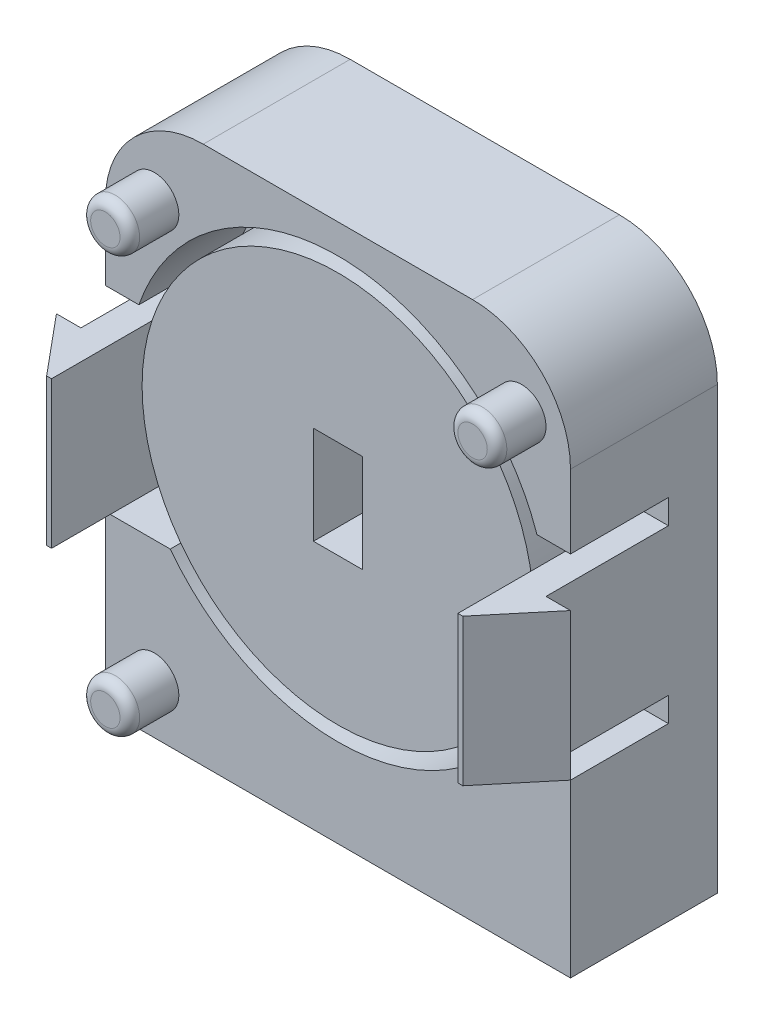
SolidWorks part; units mm, degrees
ref_plane "Front Plane" through (0, 0, 0) normal (0, 0, 1) x (1, 0, 0)
ref_plane "Top Plane" through (0, 0, 0) normal (0, 1, 0) x (1, 0, 0)
ref_plane "Right Plane" through (0, 0, 0) normal (1, 0, 0) x (0, 0, -1)
sketch "Sketch1" plane through (0, 0, 0) normal (0, 0, 1) x (1, 0, 0)
  line L1 (-4.75, -5.5) -> (4.75, -5.5)
  line L2 (-4.75, -5.5) -> (-4.75, 5.5)
  line L3 (-4.75, 5.5) -> (4.75, 5.5)
  line L4 (4.75, -5.5) -> (4.75, 5.5)
  line L5 (-4.75, -5.5) -> (4.75, 5.5) construction
  line L6 (-4.75, 5.5) -> (4.75, -5.5) construction
  point P0 (0, 0)
  dimension "D1" = 11
  dimension "D2" = 9.5
extrude "Boss-Extrude1" add sketch "Sketch1" along normal blind 3
sketch "Sketch2" plane through (0, 0, 3) normal (0, 0, 1) x (1, 0, 0)
  line L0 (0, 5.5) -> (0, -5.5) construction
  line L1 (4.75, 5.5) -> (-4.75, 5.5) construction
  line L2 (-4.75, -5.5) -> (4.75, -5.5) construction
  circle A0 centre (0, 0.6) radius 4.3
  dimension "D1" = 0.6
  dimension "D2" = 8.6
extrude "Cut-Extrude1" cut sketch "Sketch2" against normal offset from surface (2 mm away) 1 up to face at (0, 0, 0)
fillet "Fillet1" radius 2 2 edges at (-4.75, 5.5, 1.5) (4.75, 5.5, 1.5)
sketch "Sketch3" plane through (0, 0, 3) normal (0, 0, 1) x (1, 0, 0)
  line L0 (4.75, -5.5) -> (4.75, 3.5) construction
  line L1 (-4.75, 2) -> (4.75, 2)
  line L2 (-4.75, 2) -> (-4.75, -2)
  line L3 (-4.75, -2) -> (4.75, -2)
  line L4 (4.75, 2) -> (4.75, -2)
  line L5 (-4.75, 3.5) -> (-4.75, -5.5) construction
  line L6 (2.75, 5.5) -> (-2.75, 5.5) construction
  line L7 (-4.75, -5.5) -> (4.75, -5.5) construction
  dimension "D1" = 3.5
  dimension "D2" = 3.5
extrude "Cut-Extrude2" cut sketch "Sketch3" against normal up to surface (2 mm away) up to face at (-4.3, 0.6, 1)
sketch "Sketch4" plane through (0, 0, 1) normal (0, 0, 1) x (1, 0, 0)
  line L0 (-4.75, 2) -> (-4.75, -2) construction
  line L1 (-4.75, 1.5) -> (-4.15, 1.5)
  line L2 (-4.75, 1.5) -> (-4.75, -1.5)
  line L3 (-4.75, -1.5) -> (-4.15, -1.5)
  line L4 (-4.15, 1.5) -> (-4.15, -1.5)
  line L7 (-4.75, 2) -> (-4.75, 1.5) construction
  line L8 (-4.75, -1.5) -> (-4.75, -2) construction
  line L9 (4.75, -2) -> (4.75, 2) construction
  line L10 (4.75, 1.5) -> (4.15, 1.5)
  line L11 (4.75, 1.5) -> (4.75, -1.5)
  line L12 (4.75, -1.5) -> (4.15, -1.5)
  line L13 (4.15, 1.5) -> (4.15, -1.5)
  dimension "D1" = 0.6
  dimension "D2" = 3
extrude "Boss-Extrude2" add sketch "Sketch4" along normal offset from surface (3.7 mm away) 1.7 up to face at (0, 3.7161, 3) offset beyond the face yes
sketch "Sketch5" plane through (0, -1.5, 0) normal (0, -1, 0) x (1, 0, 0)
  line L2 (4.75, 4.7) -> (5.25, 4.7)
  line L3 (4.75, 4.7) -> (4.75, 3.5)
  line L4 (4.75, 3.5) -> (5.25, 3.5)
  line L5 (5.25, 4.7) -> (5.25, 3.5)
  line L6 (-4.75, 4.7) -> (-5.25, 4.7)
  line L7 (-4.75, 4.7) -> (-4.75, 3.5)
  line L8 (-4.75, 3.5) -> (-5.25, 3.5)
  line L9 (-5.25, 4.7) -> (-5.25, 3.5)
  dimension "D1" = 0.5
  dimension "D2" = 1.2
extrude "Boss-Extrude3" add sketch "Sketch5" against normal up to surface (3 mm away) up to face at (-4.45, 1.5, 2.85)
sketch "Sketch6" plane through (0, -1.5, 0) normal (0, -1, 0) x (1, 0, 0)
  line L0 (5.25, 3.5) -> (4.25, 4.7)
  line L1 (5.25, 4.7) -> (4.15, 4.7) construction
  line L2 (4.25, 4.7) -> (5.25, 4.7)
  line L3 (5.25, 4.7) -> (5.25, 3.5)
  line L4 (-5.25, 3.5) -> (-4.25, 4.7)
  line L5 (-4.15, 4.7) -> (-5.25, 4.7) construction
  line L6 (-4.25, 4.7) -> (-5.25, 4.7)
  line L7 (-5.25, 4.7) -> (-5.25, 3.5)
  dimension "D1" = 0.1
extrude "Cut-Extrude3" cut sketch "Sketch6" against normal through all
sketch "Sketch7" plane through (0, 0, 3) normal (0, 0, 1) x (1, 0, 0)
  line L2 (-4.75, -5.5) -> (4.75, -5.5) construction
  line L4 (-4.75, -2) -> (-4.75, -5.5) construction
  line L6 (-4.75, 3.5) -> (-4.75, 2) construction
  line L9 (2.75, 5.5) -> (-2.75, 5.5) construction
  line L10 (4.75, 2) -> (4.75, 3.5) construction
  circle A0 centre (-3.75, 4) radius 0.5
  circle A1 centre (3.75, 4) radius 0.5
  circle A2 centre (-3.75, -4.5) radius 0.5
  dimension "D1" = 0.5
  dimension "D2" = 0.5
  dimension "D3" = 1
  dimension "D4" = 0.5
  dimension "D5" = 1
  dimension "D6" = 0.5
extrude "Boss-Extrude4" add sketch "Sketch7" along normal blind 1
fillet "Fillet2" radius 0.2 3 edges at (-3.25, -4.5, 4) (-3.25, 4, 4) (4.25, 4, 4)
sketch "Sketch8" plane through (0, 0, 1) normal (0, 0, 1) x (1, 0, 0)
  line L1 (0.5, -0.4) -> (-0.5, -0.4)
  line L2 (0.5, -0.4) -> (0.5, 1.6)
  line L3 (0.5, 1.6) -> (-0.5, 1.6)
  line L4 (-0.5, -0.4) -> (-0.5, 1.6)
  line L5 (0.5, -0.4) -> (-0.5, 1.6) construction
  line L6 (0.5, 1.6) -> (-0.5, -0.4) construction
  circle A0 centre (0, 0.6) radius 4
  arc A1 (4.0657, 2) -> (-4.0657, 2) centre (0, 0.6) ccw construction
  dimension "D1" = 0.3
  dimension "D2" = 1
  dimension "D3" = 2
extrude "Boss-Extrude5" add sketch "Sketch8" along normal up to surface (2 mm away) up to face at (3.25, 4, 3)
